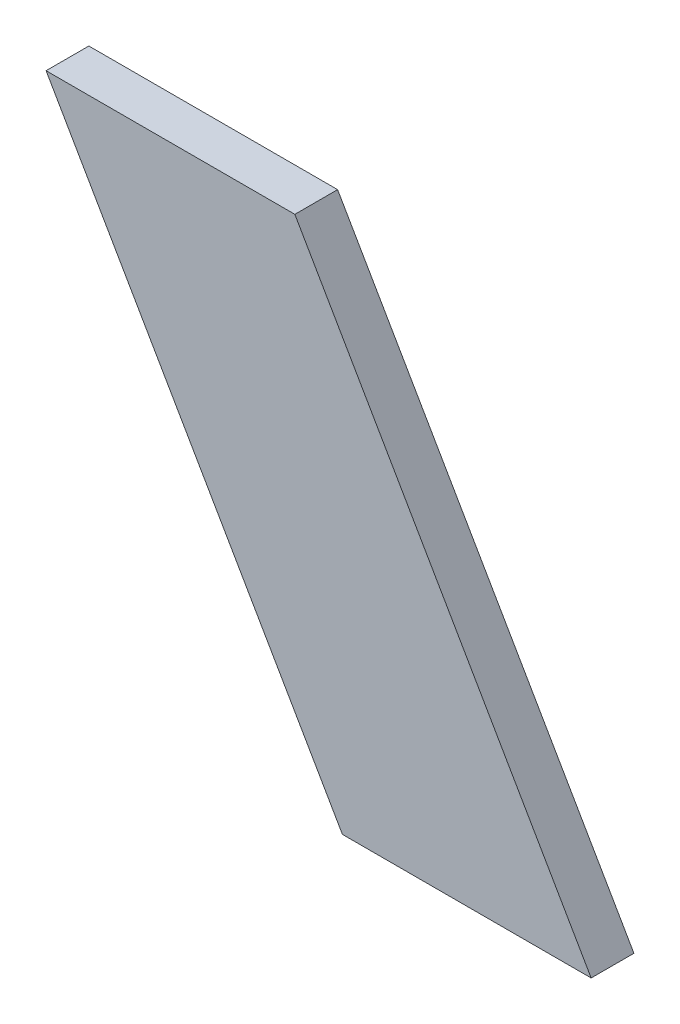
SolidWorks part; units mm, degrees
ref_plane "Front Plane" through (0, 0, 0) normal (0, 0, 1) x (1, 0, 0)
ref_plane "Top Plane" through (0, 0, 0) normal (0, 1, 0) x (1, 0, 0)
ref_plane "Right Plane" through (0, 0, 0) normal (1, 0, 0) x (0, 0, -1)
sketch "Sketch1" plane through (0, 0, 0) normal (0, 0, 1) x (1, 0, 0)
  line L0 (22.9, 0) -> (57.8, 0)
  line L1 (57.8, 0) -> (99.3692, -72)
  line L2 (99.3692, -72) -> (64.4692, -72)
  line L3 (64.4692, -72) -> (22.9, 0)
extrude "Boss-Extrude1" add sketch "Sketch1" along normal blind 3 and the other way blind 3
